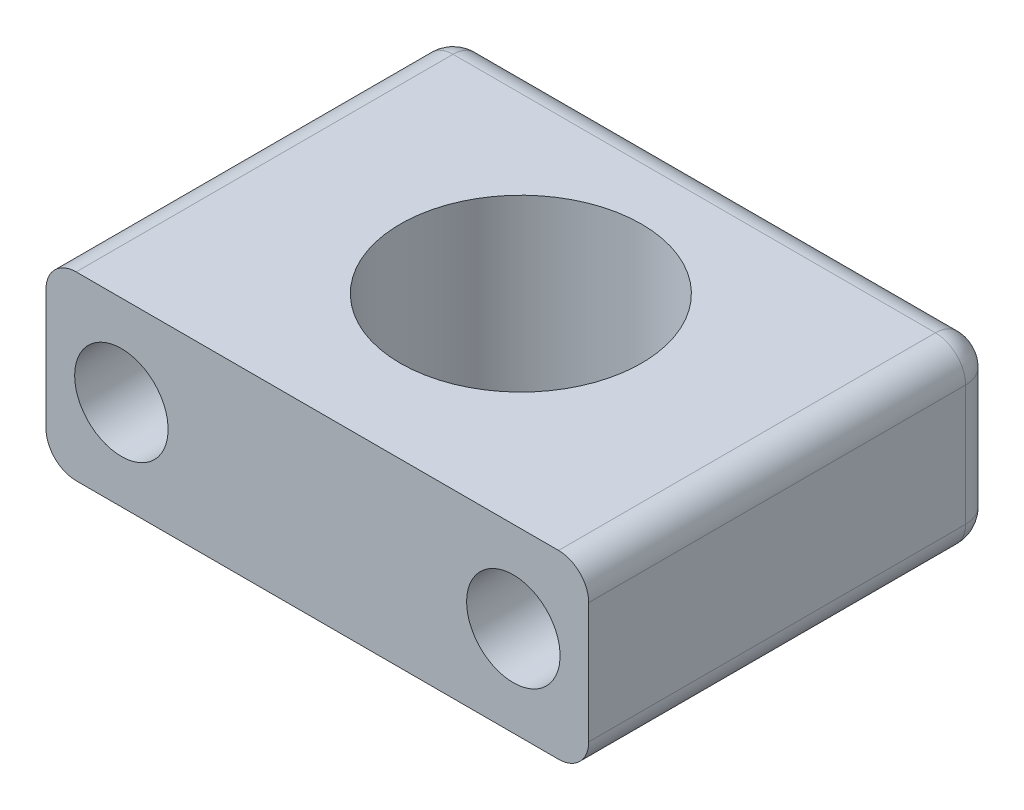
SolidWorks part; units mm, degrees
material "7075-T6 (SN)"
ref_plane "Front" through (0, 0, 0) normal (0, 0, 1) x (1, 0, 0)
ref_plane "Top" through (0, 0, 0) normal (0, 1, 0) x (1, 0, 0)
ref_plane "Right" through (0, 0, 0) normal (1, 0, 0) x (0, 0, -1)
sketch "Sketch1" plane through (0, 0, 0) normal (0, 1, 0) x (1, 0, 0)
  line L0 (-18, 0) -> (18, 0)
  line L1 (18, 0) -> (18, 27)
  line L2 (18, 27) -> (-18, 27)
  line L7 (1.5423, 13.5) -> (50001.5423, 13.5) construction
  line L8 (0, 7.5501) -> (0, 50007.5501) construction
  line L9 (-18, 27) -> (-18, 0)
  circle A2 centre (0, 13.5) radius 8
  point P4 (0, 0)
  point P20 (0, 27)
  dimension "D2" = 13.5
  dimension "D4" = 36
  dimension "D1" = 16
  dimension "D3" = 27
  dimension "D5" = 36
extrude "Boss-Extrude1" add sketch "Sketch1" along normal blind 12
sketch "Sketch3" plane through (0, 0, -27) normal (0, 0, -1) x (-1, 0, 0)
  line L0 (18, 6) -> (-18, 6) construction
  line L2 (-18, 12) -> (-18, 0) construction
  line L4 (18, 12) -> (18, 0) construction
  circle A0 centre (13, 6) radius 3.1
  circle A1 centre (-13, 6) radius 3.1
  dimension "D1" = 6.2
  dimension "D2" = 6.2
  dimension "D3" = 5
  dimension "D4" = 5
extrude "Cut-Extrude1" cut sketch "Sketch3" against normal through all
fillet "Fillet1" radius 2 8 edges at (18, 0, -13.5) (18, 12, -13.5) (18, 6, -27) (0, 0, -27) (0, 12, -27) (-18, 12, -13.5) (-18, 0, -13.5) (-18, 6, -27)
